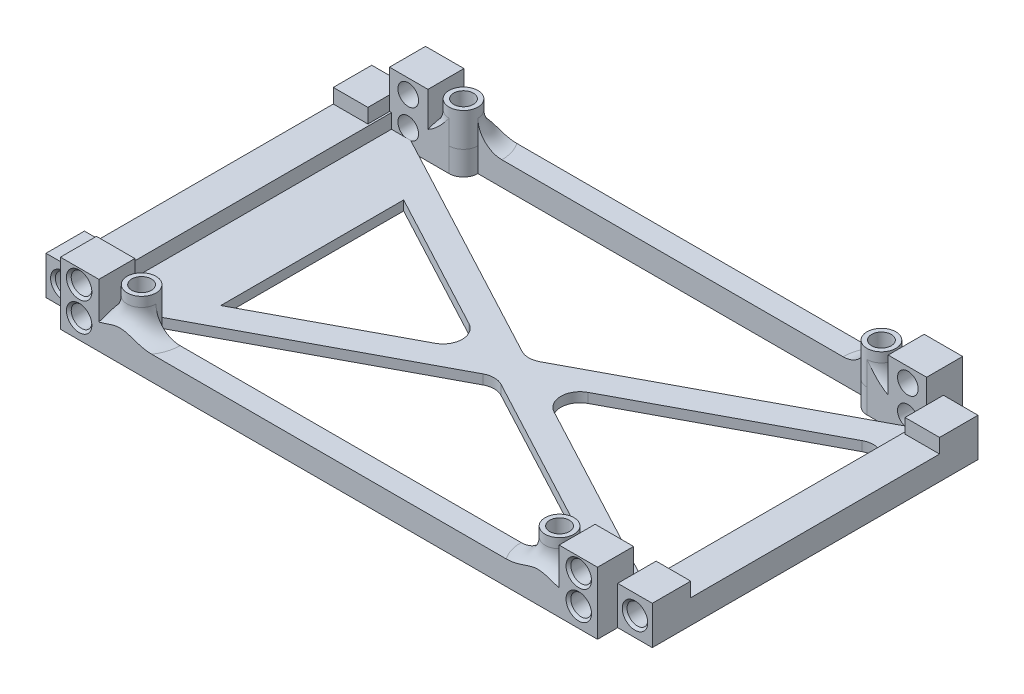
SolidWorks part; units mm, degrees
ref_plane "Front Plane" through (0, 0, 0) normal (0, 0, 1) x (1, 0, 0)
ref_plane "Top Plane" through (0, 0, 0) normal (0, 1, 0) x (1, 0, 0)
ref_plane "Right Plane" through (0, 0, 0) normal (1, 0, 0) x (0, 0, -1)
sketch "Sketch1" plane through (0, 0, 0) normal (0, 1, 0) x (1, 0, 0)
  line L0 (-70, -33.9) -> (-70, 33.9)
  line L1 (-70, -41) -> (70, -41) construction
  line L2 (-70, -41) -> (-70, 41) construction
  line L3 (-70, 41) -> (70, 41) construction
  line L4 (70, -41) -> (70, 41) construction
  line L5 (-70, -41) -> (70, 41) construction
  line L6 (-70, 41) -> (70, -41) construction
  line L7 (-70, 33.9) -> (-55.9, 33.9)
  line L8 (-55.9, 33.9) -> (-55.9, 41)
  line L9 (-55.9, 41) -> (55.9, 41)
  line L10 (55.9, 41) -> (55.9, 33.9)
  line L11 (55.9, 33.9) -> (70, 33.9)
  line L12 (70, 33.9) -> (70, -33.9)
  line L13 (70, -33.9) -> (55.9, -33.9)
  line L14 (55.9, -33.9) -> (55.9, -41)
  line L15 (55.9, -41) -> (-55.9, -41)
  line L16 (-55.9, -41) -> (-55.9, -33.9)
  line L17 (-55.9, -33.9) -> (-70, -33.9)
  point P0 (0, 0)
  dimension "D1" = 140
  dimension "D2" = 82
  dimension "D3" = 7.1
  dimension "D4" = 14.1
extrude "Boss-Extrude1" add sketch "Sketch1" along normal blind 5
sketch "Sketch3" plane through (0, 5, 0) normal (0, 1, 0) x (1, 0, 0)
  line L1 (-43.5, 33.4) -> (43.5, 33.4) construction
  line L2 (-43.5, 33.4) -> (-43.5, -33.6) construction
  line L3 (-43.5, -33.6) -> (43.5, -33.6) construction
  line L4 (43.5, 33.4) -> (43.5, -33.6) construction
  line L5 (-43.5, 33.4) -> (43.5, -33.6) construction
  line L6 (-43.5, -33.6) -> (43.5, 33.4) construction
  circle A0 centre (-43.5, -33.6) radius 3
  circle A1 centre (43.5, -33.6) radius 3
  circle A2 centre (43.5, 33.4) radius 3
  circle A3 centre (-43.5, 33.4) radius 3
  point P0 (0, -0.1)
  dimension "D4" = 6
  dimension "D1" = 87
  dimension "D2" = 67
  dimension "D3" = 0.1
sketch "Sketch2" plane through (0, 5, 0) normal (0, 1, 0) x (1, 0, 0)
  line L0 (-43.5, 30.4) -> (-40.5, 30.4)
  line L5 (-40.5, -33.6) -> (40.5, -33.6)
  line L6 (-43.5, -30.6) -> (-43.5, 30.4)
  line L7 (-40.5, 33.4) -> (40.5, 33.4)
  line L8 (43.5, -30.6) -> (43.5, 30.4)
  line L9 (-43.5, -33.6) -> (43.5, 33.4) construction
  line L10 (-43.5, 33.4) -> (43.5, -33.6) construction
  line L11 (-40.5, 30.4) -> (-40.5, 33.4)
  line L12 (40.5, 33.4) -> (40.5, 30.4)
  line L13 (40.5, 30.4) -> (43.5, 30.4)
  line L14 (43.5, -30.6) -> (40.5, -30.6)
  line L15 (40.5, -30.6) -> (40.5, -33.6)
  line L16 (-40.5, -33.6) -> (-40.5, -30.6)
  line L17 (-40.5, -30.6) -> (-43.5, -30.6)
  line L18 (43.5, -33.6) -> (-43.5, -33.6) construction
  line L19 (-43.5, -33.6) -> (-43.5, 33.4) construction
  line L20 (-43.5, 33.4) -> (43.5, 33.4) construction
  line L21 (43.5, 33.4) -> (43.5, -33.6) construction
  point P0 (0, 0)
  point P1 (0, -0.1)
  dimension "D1" = 3
extrude "Cut-Extrude1" cut sketch "Sketch2" against normal through all
extrude "Boss-Extrude2" add sketch "Sketch3" along normal blind 7
sketch "Sketch4" plane through (0, 12, 0) normal (0, 1, 0) x (1, 0, 0)
  circle A0 centre (-43.5, 33.4) radius 2.05
  circle A1 centre (43.5, 33.4) radius 2.05
  circle A2 centre (43.5, -33.6) radius 2.05
  circle A3 centre (-43.5, -33.6) radius 2.05
  dimension "D1" = 4.1
extrude "Cut-Extrude2" cut sketch "Sketch4" against normal through all and the other way through all
sketch "Sketch5" plane through (0, 5, 0) normal (0, 1, 0) x (1, 0, 0)
  line L0 (-43.5, -30.6) -> (-40.5, -30.6) construction
  line L1 (-43.5, 30.4) -> (-55.5, 30.4)
  line L2 (-43.5, 30.4) -> (-43.5, -30.6)
  line L3 (-43.5, -30.6) -> (-55.5, -30.6)
  line L4 (-55.5, 30.4) -> (-55.5, -30.6)
  line L5 (0, 33.4) -> (0, -33.6) construction
  line L6 (40.5, 33.4) -> (-40.5, 33.4) construction
  line L7 (-40.5, -33.6) -> (40.5, -33.6) construction
  line L8 (55.5, 30.4) -> (55.5, -30.6)
  line L9 (43.5, -30.6) -> (55.5, -30.6)
  line L10 (43.5, 30.4) -> (43.5, -30.6)
  line L11 (43.5, 30.4) -> (55.5, 30.4)
  dimension "D1" = 12
extrude "Cut-Extrude3" cut sketch "Sketch5" against normal through all
fillet "Fillet1" radius 3 4 edges at (40.5, 2.5, 30.6) (-40.5, 2.5, 30.6) (40.5, 2.5, -30.4) (-40.5, 2.5, -30.4)
sketch "Sketch6" plane through (0, 5, 0) normal (0, 1, 0) x (1, 0, 0)
  line L0 (40.5, 33.4) -> (-40.5, 33.4) construction
  line L1 (-25, 33.4) -> (25, 33.4)
  line L2 (-25, 33.4) -> (-25, 33.6)
  line L3 (-25, 33.6) -> (25, 33.6)
  line L4 (25, 33.4) -> (25, 33.6)
  line L5 (0, -33.6) -> (0, -41) construction
  line L6 (-40.5, -33.6) -> (40.5, -33.6) construction
  line L7 (-55.9, -41) -> (55.9, -41) construction
  line L8 (0, 33.6) -> (0, 41) construction
  line L9 (55.9, 41) -> (-55.9, 41) construction
  point P6 (0, 33.6)
  dimension "D1" = 50
sketch "Sketch7" plane through (0, 5, 0) normal (0, 1, 0) x (1, 0, 0)
  line L0 (0, 41) -> (0, -41) construction
  line L1 (55.9, 33.9) -> (63.1, 33.9)
  line L2 (55.9, 33.9) -> (55.9, 25.9)
  line L3 (55.9, 25.9) -> (63.1, 25.9)
  line L4 (63.1, 33.9) -> (63.1, 25.9)
  line L5 (55.9, 41) -> (-55.9, 41) construction
  line L6 (-55.9, -41) -> (55.9, -41) construction
  line L7 (-70, 0) -> (70, 0) construction
  line L8 (-70, 33.9) -> (-70, -33.9) construction
  line L9 (70, -33.9) -> (70, 33.9) construction
  dimension "D1" = 7.2
  dimension "D2" = 8
extrude "Boss-Extrude3" add sketch "Sketch7" along normal blind 3
sketch "Sketch8" plane through (0, 0, -33.9) normal (0, 0, -1) x (-1, 0, 0)
  line L0 (-63.1, 8) -> (-55.9, 0) construction
  circle A0 centre (-59.5, 4) radius 2.15
  dimension "D1" = 4.3
extrude "Cut-Extrude5" cut sketch "Sketch8" against normal blind 6
mirror "Mirror3" about plane through (0, 0, 0) normal (1, 0, 0) of "Cut-Extrude5", "Boss-Extrude3"
mirror "Mirror4" about plane through (0, 0, 0) normal (0, 0, 1) of "Mirror3", "Boss-Extrude3", "Cut-Extrude5"
sketch "Sketch10" plane through (0, 5, 0) normal (0, 1, 0) x (1, 0, 0)
  line L0 (55.9, 33.9) -> (55.9, 41) construction
  line L1 (-55.9, 41) -> (55.9, 41)
  line L2 (-55.9, 41) -> (-55.9, 40)
  line L3 (-55.9, 40) -> (55.9, 40)
  line L4 (55.9, 41) -> (55.9, 40)
  line L5 (-55.9, -33.9) -> (-55.9, -41) construction
  line L6 (55.9, -41) -> (-55.9, -41)
  line L7 (55.9, -41) -> (55.9, -40)
  line L8 (55.9, -40) -> (-55.9, -40)
  line L9 (-55.9, -41) -> (-55.9, -40)
  dimension "D1" = 1
  dimension "D2" = 1
extrude "Cut-Extrude7" cut sketch "Sketch10" against normal through all
sketch "Sketch13" plane through (0, 5, 0) normal (0, 1, 0) x (1, 0, 0)
  line L0 (55.9, 33.9) -> (55.9, 40) construction
  line L1 (-55.9, 40) -> (55.9, 40)
  line L2 (-55.9, 40) -> (-55.9, 39.4)
  line L3 (-55.9, 39.4) -> (55.9, 39.4)
  line L4 (55.9, 40) -> (55.9, 39.4)
  line L5 (-55.9, -33.9) -> (-55.9, -40) construction
  line L6 (55.9, -40) -> (-55.9, -40)
  line L7 (55.9, -40) -> (55.9, -39.6)
  line L8 (55.9, -39.6) -> (-55.9, -39.6)
  line L9 (-55.9, -40) -> (-55.9, -39.6)
  dimension "D1" = 0.6
  dimension "D2" = 0.4
extrude "Cut-Extrude9" cut sketch "Sketch13" against normal through all both and the other way through all
sketch "Sketch14" plane through (0, 5, 0) normal (0, 1, 0) x (1, 0, 0)
  line L0 (-43.5, 30.4) -> (-55.5, 30.4) construction
  line L1 (-55.9, -39.6) -> (-47.9, -39.6)
  line L2 (-55.9, -39.6) -> (-55.9, -30.6)
  line L3 (-55.9, -30.6) -> (-47.9, -30.6)
  line L4 (-47.9, -39.6) -> (-47.9, -30.6)
  line L5 (-55.9, 39.4) -> (-47.9, 39.4)
  line L6 (-55.9, 39.4) -> (-55.9, 30.4)
  line L7 (-55.9, 30.4) -> (-47.9, 30.4)
  line L8 (-47.9, 39.4) -> (-47.9, 30.4)
  dimension "D1" = 8
extrude "Boss-Extrude5" add sketch "Sketch14" along normal blind 8
sketch "Sketch15" plane through (0, 0, 39.6) normal (0, 0, 1) x (1, 0, 0)
  line L0 (-47.9, 5) -> (-47.9, 0) construction
  line L1 (55.9, 0) -> (-55.9, 0) construction
  line L3 (-55.9, 0) -> (-55.9, 13) construction
  circle A0 centre (-52, 4) radius 2.15
  circle A1 centre (-52, 10) radius 2.15
  dimension "D1" = 4.3
  dimension "D2" = 3.9
  dimension "D3" = 6
  dimension "D4" = 4
extrude "Cut-Extrude10" cut sketch "Sketch15" against normal through all
mirror "Mirror5" about plane through (0, 0, 0) normal (1, 0, 0) of "Boss-Extrude5", "Cut-Extrude10"
sketch "Sketch16" plane through (0, 13, 0) normal (0, 1, 0) x (1, 0, 0)
  line L0 (55.9, -79.1) -> (55.9, 39.4) construction
  line L1 (-55.9, 39.4) -> (55.9, 39.4)
  line L2 (-55.9, 39.4) -> (-55.9, 37.9)
  line L3 (-55.9, 37.9) -> (55.9, 37.9)
  line L4 (55.9, 39.4) -> (55.9, 37.9)
  line L5 (-55.9, -30.6) -> (-55.9, -39.6) construction
  line L6 (55.9, -39.6) -> (-55.9, -39.6)
  line L7 (55.9, -39.6) -> (55.9, -38.1)
  line L8 (55.9, -38.1) -> (-55.9, -38.1)
  line L9 (-55.9, -39.6) -> (-55.9, -38.1)
  dimension "D1" = 1.5
  dimension "D2" = 1.5
extrude "Cut-Extrude11" cut sketch "Sketch16" against normal through all
fillet "Fillet2" radius 5 4 edges at (45.6213, 5, -35.5213) (-45.6213, 5, -35.5213) (45.6213, 5, 35.7213) (-45.6213, 5, 35.7213)
sketch "Sketch17" plane through (0, 0, 0) normal (0, -1, 0) x (1, 0, 0)
  line L0 (-55.5, 26.6) -> (-5.7544, 0.1)
  line L1 (-55.5, -30.4) -> (-55.5, 30.6) construction
  line L2 (55.5, -30.4) -> (43.5, -30.4) construction
  line L3 (51.5, -30.4) -> (55.5, -30.4)
  line L4 (55.5, -30.4) -> (55.5, -26.4)
  line L5 (55.5, 30.6) -> (55.5, -30.4) construction
  line L6 (55.5, -26.4) -> (5.7544, 0.1)
  line L7 (-55.5, 30.6) -> (-43.5, 30.6) construction
  line L8 (-51.5, 30.6) -> (-55.5, 30.6)
  line L9 (-55.5, 30.6) -> (-55.5, 26.6)
  line L10 (-55.5, -30.4) -> (-51.5, -30.4)
  line L11 (-43.5, -30.4) -> (-55.5, -30.4) construction
  line L12 (-51.5, -30.4) -> (0, -2.9654)
  line L13 (55.5, 26.6) -> (55.5, 30.6)
  line L14 (55.5, 30.6) -> (51.5, 30.6)
  line L15 (43.5, 30.6) -> (55.5, 30.6) construction
  line L16 (51.5, 30.6) -> (0, 3.1654)
  line L17 (-55.5, -26.4) -> (-55.5, -30.4)
  line L18 (-5.7544, 0.1) -> (-55.5, -26.4)
  line L19 (5.7544, 0.1) -> (55.5, 26.6)
  line L20 (0, 3.1654) -> (-51.5, 30.6)
  line L21 (0, -2.9654) -> (51.5, -30.4)
  dimension "D1" = 4
extrude "Boss-Extrude6" add sketch "Sketch17" against normal blind 2
fillet "Fillet3" radius 4 8 edges at (5.7544, 1, 0.1) (0, 1, 3.1654) (0, 1, -2.9654) (55.5, 1, -26.4) (55.5, 1, 26.6) (-55.5, 1, 26.6) (-5.7544, 1, 0.1) (-55.5, 1, -26.4)
chamfer "Chamfer1" distance 0.5 angle 45 12 edges at (49.85, 4, 38.1) (49.85, 10, 38.1) (57.35, 4, 33.9) (-54.15, 10, 38.1) (-54.15, 4, 38.1) (-57.35, 4, 33.9) (57.35, 4, -33.9) (-57.35, 4, -33.9) (-49.85, 10, -37.9) (-49.85, 4, -37.9) (54.15, 4, -37.9) (54.15, 10, -37.9)
sketch "Sketch18" plane through (0, 2, 0) normal (0, 1, 0) x (1, 0, 0)
  line L0 (-55.5, 19.737) -> (-55.5, 30.4) construction
  line L1 (-55.5, 25.0685) -> (-41.4917, 25.0685)
  line L2 (-55.5, 25.0685) -> (-55.5, -25.0685)
  line L3 (-55.5, -25.0685) -> (-41.4917, -25.0685)
  line L4 (-41.4917, 25.0685) -> (-41.4917, -25.0685)
  line L5 (-51.5, 30.4) -> (-1.8806, 3.9673) construction
  point P6 (-41.4917, 0)
extrude "Boss-Extrude7" add sketch "Sketch18" against normal up to surface (2 mm away) up to face at (0, 0, -24.3278)
sketch "Sketch19" plane through (0, 5, 0) normal (0, 1, 0) x (1, 0, 0)
  line L1 (-70, 33.9) -> (-63.1, 33.9)
  line L2 (-70, 33.9) -> (-70, -33.9)
  line L3 (-70, -33.9) -> (-63.1, -33.9)
  line L4 (-63.1, 33.9) -> (-63.1, -33.9)
  line L5 (70, 33.9) -> (63.1, 33.9)
  line L6 (70, 33.9) -> (70, -33.9)
  line L7 (70, -33.9) -> (63.1, -33.9)
  line L8 (63.1, 33.9) -> (63.1, -33.9)
extrude "Cut-Extrude12" cut sketch "Sketch19" against normal through all
